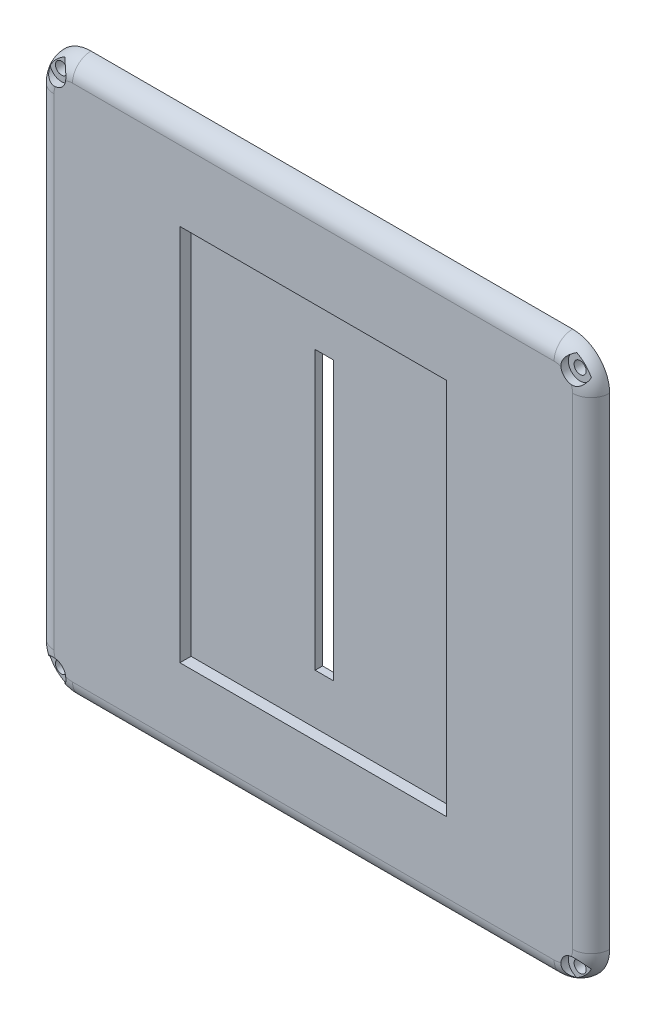
SolidWorks part; units mm, degrees
ref_plane "Alzado" through (0, 0, 0) normal (0, 0, 1) x (1, 0, 0)
ref_plane "Planta" through (0, 0, 0) normal (0, 1, 0) x (1, 0, 0)
ref_plane "Vista lateral" through (0, 0, 0) normal (1, 0, 0) x (0, 0, -1)
sketch "Croquis1" plane through (0, 0, 0) normal (0, 0, 1) x (1, 0, 0)
  line L1 (-75, 75) -> (75, 75)
  line L2 (-75, 75) -> (-75, -75)
  line L3 (-75, -75) -> (75, -75)
  line L4 (75, 75) -> (75, -75)
  line L5 (-75, 75) -> (75, -75) construction
  line L6 (-75, -75) -> (75, 75) construction
  point P0 (0, 0)
  dimension "D1" = 150
  dimension "D2" = 150
extrude "Saliente-Extruir1" add sketch "Croquis1" along normal blind 5
sketch "Croquis2" plane through (0, 0, 5) normal (0, 0, 1) x (1, 0, 0)
  line L0 (-75, -75) -> (75, -75) construction
  line L1 (75, -75) -> (0, -75) construction
  line L2 (0, -75) -> (0, 75) construction
  line L3 (75, 75) -> (-75, 75) construction
  line L5 (-36, 51) -> (36, 51)
  line L6 (-36, 51) -> (-36, -51)
  line L7 (-36, -51) -> (36, -51)
  line L8 (36, 51) -> (36, -51)
  line L9 (-36, 51) -> (36, -51) construction
  line L10 (-36, -51) -> (36, 51) construction
  point P8 (0, 0)
  dimension "D1" = 102
  dimension "72" = 72
extrude "Cortar-Extruir1" cut sketch "Croquis2" against normal blind 3
sketch "Croquis3" plane through (0, 0, 5) normal (0, 0, 1) x (1, 0, 0)
  line L1 (-2.5, 37.5) -> (2.5, 37.5)
  line L2 (-2.5, 37.5) -> (-2.5, -37.5)
  line L3 (-2.5, -37.5) -> (2.5, -37.5)
  line L4 (2.5, 37.5) -> (2.5, -37.5)
  line L5 (-2.5, 37.5) -> (2.5, -37.5) construction
  line L6 (-2.5, -37.5) -> (2.5, 37.5) construction
  point P0 (0, 0)
  dimension "D1" = 75
  dimension "D2" = 5
extrude "Cortar-Extruir2" cut sketch "Croquis3" against normal blind 10
fillet "Redondeo1" radius 10 4 edges at (75, 75, 2.5) (-75, 75, 2.5) (-75, -75, 2.5) (75, -75, 2.5)
fillet "Redondeo3" radius 5 8 edges at (72.0711, 72.0711, 5) (75, 0, 5) (72.0711, -72.0711, 5) (0, -75, 5) (-72.0711, -72.0711, 5) (-75, 0, 5) (-72.0711, 72.0711, 5) (0, 75, 5)
sketch "Croquis6" plane through (0, 0, 5) normal (0, 0, 1) x (1, 0, 0)
  line L0 (0, 0) -> (70, 0) construction
  line L1 (70, -65) -> (70, 65) construction
  line L2 (70, 0) -> (-70, 0) construction
  line L3 (-70, 65) -> (-70, -65) construction
  line L5 (-70, -70) -> (70, -70)
  line L6 (-70, -70) -> (-70, 70)
  line L7 (-70, 70) -> (70, 70)
  line L8 (70, -70) -> (70, 70)
  line L9 (-70, -70) -> (70, 70) construction
  line L10 (-70, 70) -> (70, -70) construction
  dimension "D1" = 140
  dimension "D2" = 140
hole_wizard "Refrentado para tornillo con cabeza troncocónica de #41" positions "Croquis10" profile "Croquis11" counterbore size "#4" standard "Ansi Inch"
sketch "Croquis10" plane through (0, 0, 5) normal (0, 0, 1) x (1, 0, 0)
  point P0 (-70, 70)
  point P3 (-70, -70)
  point P6 (70, -70)
  point P9 (70, 70)
sketch "Croquis11" plane through (-70, 70, 5) normal (1, 0, 0) x (0, -1, 0)
  line L0 (0, 0) -> (0, 50.9806)
  line L1 (0, 50.9806) -> (1.6319, 50)
  line L2 (1.6319, 50) -> (1.6319, 2.032)
  line L3 (1.6319, 2.032) -> (3.175, 2.032)
  line L4 (3.175, 2.032) -> (3.175, 0)
  line L5 (3.175, 0) -> (0, 0)
  line L10 (0, 50.9806) -> (-1.632, 50) construction
  line L11 (0, -6.35) -> (0, 107.95) construction
  dimension "Diámetro de taladro" = 3.2639
  dimension "Profundidad de taladro" = 50
  dimension "Diámetro de refrentado" = 6.35
  dimension "Profundidad de refrentado" = 2.032
  dimension "Ángulo de perforador" = 118
